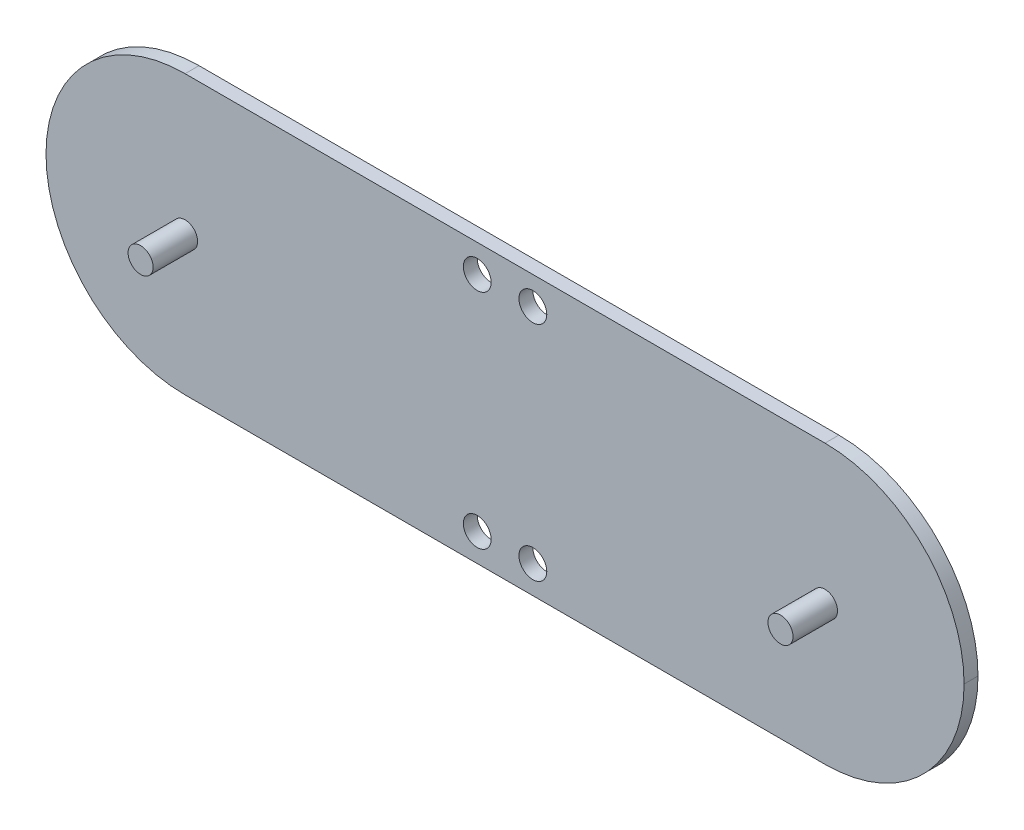
SolidWorks part; units mm, degrees
ref_plane "Front Plane" through (0, 0, 0) normal (0, 0, 1) x (1, 0, 0)
ref_plane "Top Plane" through (0, 0, 0) normal (0, 1, 0) x (1, 0, 0)
ref_plane "Right Plane" through (0, 0, 0) normal (1, 0, 0) x (0, 0, -1)
sketch "Sketch1" plane through (0, 0, 0) normal (0, 0, 1) x (1, 0, 0)
  line L1 (82.5, 25) -> (-82.5, 25)
  line L2 (82.5, 25) -> (82.5, -25)
  line L3 (82.5, -25) -> (-82.5, -25)
  line L4 (-82.5, 25) -> (-82.5, -25)
  line L5 (82.5, 25) -> (-82.5, -25) construction
  line L6 (82.5, -25) -> (-82.5, 25) construction
  point P0 (0, 0)
  dimension "D1" = 50
  dimension "D2" = 165
extrude "Boss-Extrude1" add sketch "Sketch1" along normal blind 2.5
fillet "Fillet1" radius 25 4 edges at (-82.5, -25, 1.25) (-82.5, 25, 1.25) (82.5, -25, 1.25) (82.5, 25, 1.25)
sketch "Sketch2" plane through (0, 0, 2.5) normal (0, 0, 1) x (1, 0, 0)
  line L0 (0, 0) -> (0, 20)
  line L1 (0, 20) -> (-5, 20)
  line L2 (-5, 20) -> (5, 20)
  circle A0 centre (-5, 20) radius 2.5
  circle A1 centre (5, 20) radius 2.5
  dimension "D4" = 5
  dimension "D5" = 5
  dimension "D1" = 20
  dimension "D2" = 5
  dimension "D3" = 10
extrude "Cut-Extrude1" cut sketch "Sketch2" against normal blind 2.5 contours A0 | A1 region at (-7.4293, 20, 2.5) region at (5, 22.4293, 2.5)
mirror "Mirror1" about plane through (0, 0, 0) normal (0, 1, 0) of "Cut-Extrude1"
sketch "Sketch4" plane through (0, 0, 2.5) normal (0, 0, 1) x (1, 0, 0)
  line L0 (0, 0) -> (-57.5, 0)
  circle A0 centre (-57.5, 0) radius 2.25
  dimension "D2" = 4.5
  dimension "D1" = 57.5
extrude "Boss-Extrude2" add sketch "Sketch4" along normal blind 8 contours A0 region at (-59.6864, 0, 2.5)
mirror "Mirror3" about plane through (0, 0, 0) normal (1, 0, 0) of "Boss-Extrude2"
